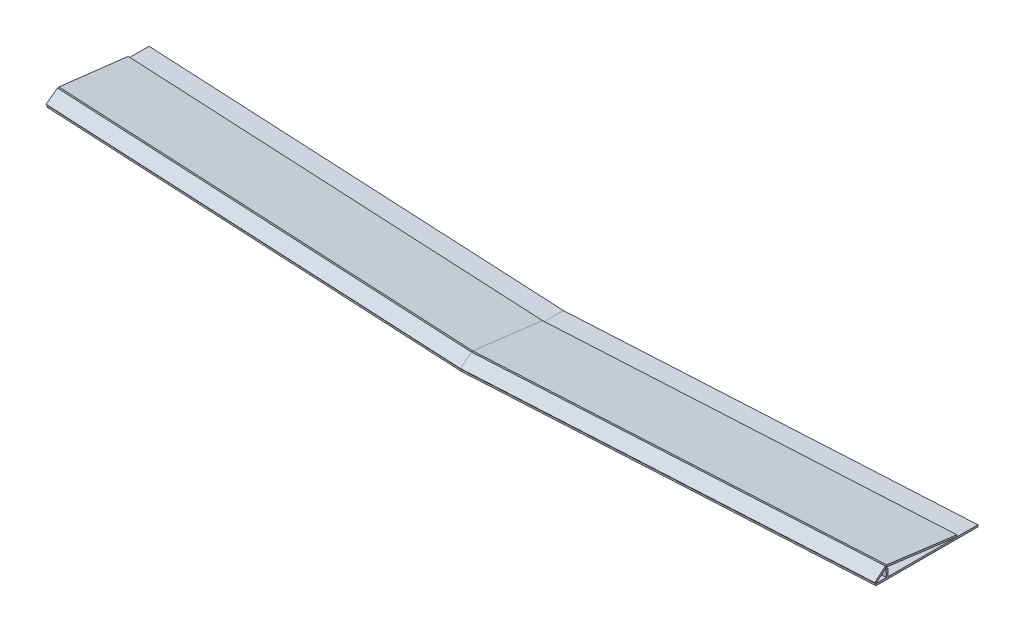
SolidWorks part; units mm, degrees
ref_plane "Front Plane" through (0, 0, 0) normal (0, 0, 1) x (1, 0, 0)
ref_plane "Top Plane" through (0, 0, 0) normal (0, 1, 0) x (1, 0, 0)
ref_plane "Right Plane" through (0, 0, 0) normal (1, 0, 0) x (0, 0, -1)
ref_axis "Axis1" through (0, 0, 10.3085) along (0, 0, -1)
ref_plane "Plane3" through (0, 0, 0) normal (0.9986, 0.0523, 0) x (0, 0, -1)
sketch "Sketch1" plane through (0, 0, 0) normal (0.9986, 0.0523, 0) x (0, 0, -1)
  line L0 (-10.3085, 0) -> (133.5385, 0) construction
  line L1 (0, 0) -> (184.15, 0)
  line L2 (0, 0) -> (0, 3.175)
  line L3 (0, 3.175) -> (184.15, 3.175)
  line L4 (184.15, 0) -> (184.15, 3.175)
  line L5 (0, 3.175) -> (20.0163, 18.8117)
  line L6 (0, 3.175) -> (-1.9546, 5.677)
  line L7 (20.0163, 18.8117) -> (18.0617, 21.3138)
  line L8 (-1.9546, 5.677) -> (18.0617, 21.3138)
  line L9 (20.0163, 18.8117) -> (146.05, 3.175)
  line L10 (20.0163, 18.8117) -> (20.4072, 21.9626)
  line L11 (146.05, 3.175) -> (146.4409, 6.3258)
  line L12 (20.4072, 21.9626) -> (146.4409, 6.3258)
  line L13 (19.05, 3.175) -> (22.225, 3.175)
  line L14 (19.05, 3.175) -> (19.05, 15.875)
  line L15 (22.225, 3.175) -> (22.225, 15.875)
  line L16 (19.05, 15.875) -> (22.225, 15.875)
  dimension "D1" = 3.175
  dimension "D2" = 3.175
  dimension "D3" = 3.175
  dimension "D4" = 25.4
  dimension "D5" = 127
  dimension "D6" = 146.05
  dimension "D7" = 184.15
  dimension "D8" = 12.7
  dimension "D9" = 19.05
  dimension "D10" = 3.175
extrude "Boss-Extrude4" add sketch "Sketch1" along normal blind 749.3 contours L5 L14 L7 L8 L6 | L10 L16 L15 L9 L11 L12 | L1 L4 L3 L2 | L3 L15 L9 L5 L14 | L16 L10 L9 L15 | L14 L5 L7 | L2 L1 L4 L3 | L5 L6 L8 L7 | L9 L10 L12 L11 region at (-0.0831, 1.5853, -92.075) region at (-0.6408, 12.2276, -9.0309) region at (-0.4985, 9.5119, -20.6375) region at (-0.6578, 12.5516, -83.2286)
extrude "Boss-Extrude6" add sketch "Sketch1<3>" along normal blind 749.3 separate body contours L3 L15 L9 L5 L14 | L15 L16 L14 L13 region at (-0.4985, 9.5119, -20.6375)
sketch "Sketch1<3>" plane through (0, 0, 0) normal (0.9986, 0.0523, 0) x (0, 0, -1) same geometry as "Sketch1"
mirror "Mirror5" about plane through (0, 0, 0) normal (1, 0, 0) of bodies 141 134 135 142 132 133
